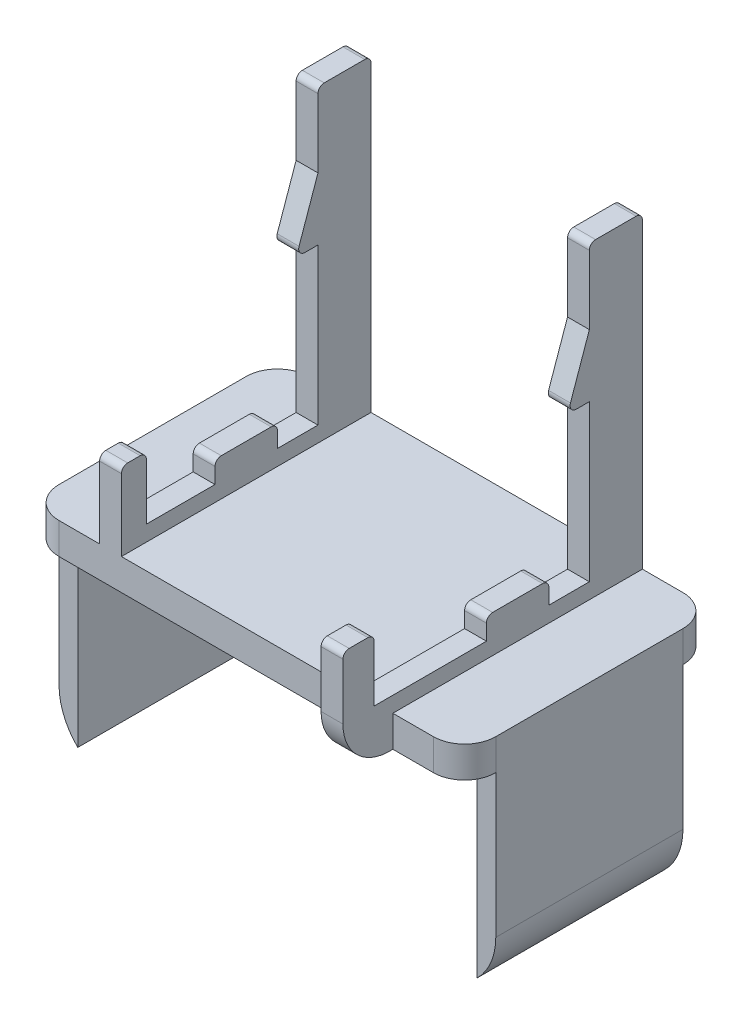
SolidWorks part; units mm, degrees
ref_plane "Front Plane" through (0, 0, 0) normal (0, 0, 1) x (1, 0, 0)
ref_plane "Top Plane" through (0, 0, 0) normal (0, 1, 0) x (1, 0, 0)
ref_plane "Right Plane" through (0, 0, 0) normal (1, 0, 0) x (0, 0, -1)
sketch "Sketch1" plane through (0, 0, 0) normal (0, 1, 0) x (1, 0, 0)
  line L1 (5, 0) -> (65, 0)
  line L2 (0, 5) -> (0, 35)
  line L3 (5, 40) -> (65, 40)
  line L4 (70, 5) -> (70, 35)
  arc A0 (70, 5) -> (65, 0) centre (65, 5) cw
  arc A1 (5, 0) -> (0, 5) centre (5, 5) cw
  arc A2 (5, 40) -> (0, 35) centre (5, 35) ccw
  arc A3 (65, 40) -> (70, 35) centre (65, 35) cw
  point P7 (70, 0)
  point P10 (0, 0)
  point P13 (0, 40)
  dimension "D3" = 5
  dimension "D1" = 70
  dimension "D2" = 40
extrude "Boss-Extrude1" add sketch "Sketch1" along normal blind 5
sketch "Sketch2" plane through (0, 0, 0) normal (0, -1, 0) x (1, 0, 0)
  line L1 (0, -5) -> (3, -5)
  line L2 (0, -5) -> (0, -35)
  line L3 (0, -35) -> (3, -35)
  line L4 (3, -5) -> (3, -35)
  line L5 (70, -5) -> (67, -5)
  line L6 (70, -5) -> (70, -35)
  line L7 (70, -35) -> (67, -35)
  line L8 (67, -5) -> (67, -35)
  dimension "D1" = 3
extrude "Boss-Extrude2" add sketch "Sketch2" along normal blind 30
fillet "Fillet1" radius 10 2 edges at (0, -30, -20) (70, -30, -20)
ref_plane "Plane1" through (35, 0, 0) normal (-1, 0, 0) x (0, 0, 1)
ref_plane "Plane2" through (15, 0, 0) normal (-1, 0, 0) x (0, 0, 1)
ref_plane "Plane3" through (55, 0, 0) normal (-1, 0, 0) x (0, 0, 1)
sketch "Sketch3" plane through (15, 0, 0) normal (-1, 0, 0) x (0, 0, 1)
  line L0 (-31.5, 7.5) -> (-31.5, 32.5)
  line L1 (-31.5, 7.5) -> (-25, 7.5)
  line L2 (-31.5, 32.5) -> (-28, 32.5)
  line L3 (-28, 32.5) -> (-31.5, 42.5)
  line L4 (-31.5, 42.5) -> (-31.5, 54.5)
  line L5 (-25, 7.5) -> (-25, 11)
  line L6 (-25, 11) -> (-15, 11)
  line L7 (-15, 11) -> (-15, 7.5)
  line L8 (-15, 7.5) -> (-4, 7.5)
  line L9 (-4, 7.5) -> (-4, 17.5)
  line L10 (0, 5) -> (-40, 5)
  line L11 (-4, 17.5) -> (0, 17.5)
  line L12 (0, 17.5) -> (0, 5)
  line L13 (-31.5, 54.5) -> (-40, 54.5)
  line L14 (-40, 54.5) -> (-40, 5)
  line L15 (-40, 5) -> (-40, 0) construction
  line L16 (-35, 5) -> (-5, 5) construction
  point P15 (0, 0)
  point P16 (-38.5902, 14.1864)
  point P20 (-20, 5)
  point P21 (-20, 11)
  dimension "D1" = 6.5
  dimension "D2" = 3.5
  dimension "D3" = 10
  dimension "D4" = 12
  dimension "D5" = 10
  dimension "D6" = 3.5
  dimension "D7" = 11
  dimension "D8" = 10
  dimension "D9" = 40
  dimension "D10" = 2.5
  dimension "D11" = 25
extrude "Boss-Extrude3" add sketch "Sketch3" along normal blind 3.5 contours L13 L14 L10 L12 L11 L9 L8 L7 L6 L5 L1 L0 L2 L3 L4 | L10 region at (15, 6.8636, -28.25)
sketch "Sketch4" plane through (55, 0, 0) normal (-1, 0, 0) x (0, 0, 1)
  line L0 (-31.5, 7.5) -> (-31.5, 32.5)
  line L1 (-31.5, 7.5) -> (-25, 7.5)
  line L2 (-31.5, 32.5) -> (-28, 32.5)
  line L3 (-28, 32.5) -> (-31.5, 42.5)
  line L4 (-31.5, 42.5) -> (-31.5, 54.5)
  line L5 (-25, 7.5) -> (-25, 11)
  line L6 (-25, 11) -> (-15, 11)
  line L7 (-15, 11) -> (-15, 7.5)
  line L8 (-15, 7.5) -> (3, 7.5)
  line L9 (3, 7.5) -> (3, 17.5)
  line L10 (0, 5) -> (-40, 5)
  line L11 (3, 17.5) -> (8, 17.5)
  line L12 (8, 17.5) -> (8, 7.5)
  line L13 (-31.5, 54.5) -> (-40, 54.5)
  line L14 (-40, 54.5) -> (-40, 5)
  line L16 (-5, 5) -> (-35, 5) construction
  line L17 (-40, 54.5) -> (-40, 5) construction
  line L18 (0, 5) -> (0, 0)
  arc A0 (8, 7.5) -> (0, 0) centre (0.4844, 7.5) cw
  point P22 (-20, 5)
  point P23 (-20, 11)
  dimension "D1" = 6.5
  dimension "D2" = 3.5
  dimension "D3" = 10
  dimension "D4" = 12
  dimension "D5" = 10
  dimension "D6" = 3.5
  dimension "D7" = 18
  dimension "D8" = 10
  dimension "D9" = 2.5
  dimension "D10" = 40
  dimension "D11" = 25
  dimension "D14" = 5
extrude "Boss-Extrude4" add sketch "Sketch4" against normal blind 3.5
fillet "Fillet2" radius 1 14 edges at (56.75, 11, -15) (56.75, 11, -25) (13.25, 11, -25) (13.25, 11, -15) (13.25, 17.5, -4) (13.25, 17.5, 0) (56.75, 17.5, 3) (56.75, 17.5, 8) (13.25, 32.5, -28) (56.75, 32.5, -28) (13.25, 54.5, -40) (13.25, 54.5, -31.5) (56.75, 54.5, -31.5) (56.75, 54.5, -40)
